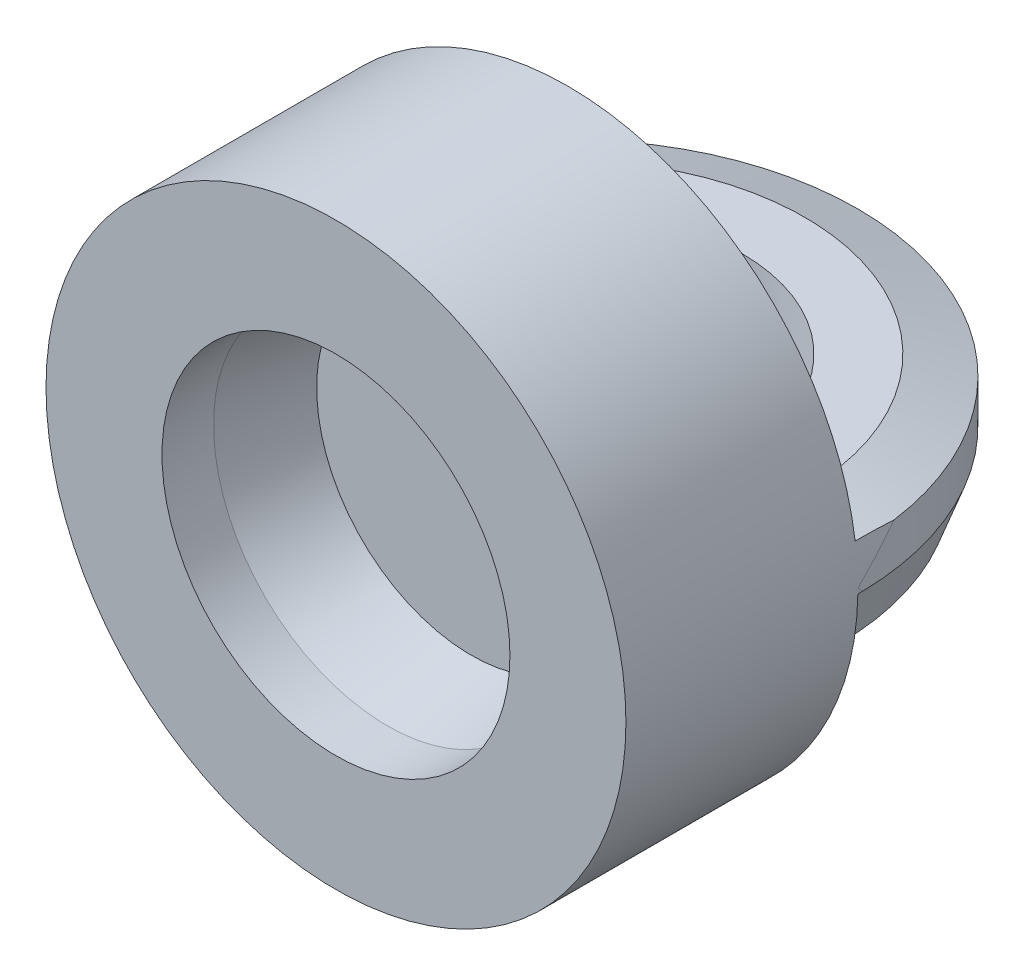
SolidWorks part; units mm, degrees
ref_plane "Front Plane" through (0, 0, 0) normal (0, 0, 1) x (1, 0, 0)
ref_plane "Top Plane" through (0, 0, 0) normal (0, 1, 0) x (1, 0, 0)
ref_plane "Right Plane" through (0, 0, 0) normal (1, 0, 0) x (0, 0, -1)
sketch "Sketch1" plane through (0, 0, 0) normal (0, 0, 1) x (1, 0, 0)
  circle A0 centre (0, 0) radius 7.5
  dimension "D1" = 15
extrude "Boss-Extrude1" add sketch "Sketch1" along normal blind 6
sketch "Sketch2" plane through (0, 0, 6) normal (0, 0, 1) x (1, 0, 0)
  circle A0 centre (0, 0) radius 4.5
  dimension "D1" = 9
extrude "Cut-Extrude1" cut sketch "Sketch2" against normal blind 3.5
chamfer "Chamfer1" distance 0.5 angle 77 1 edges at (4.5, 0, 2.5) first distance on face at (4.5, 0, 2.5)
sketch "Sketch3" plane through (0, 0, 0) normal (0, 1, 0) x (1, 0, 0)
  line L0 (7.5, 0) -> (-7.5, 0) construction
  line L1 (-7.5, 0) -> (-7.5, -6) construction
  line L2 (-7.5, 0) -> (-4.5, 0)
  line L3 (4.5, 0) -> (7.5, 0)
  arc A0 (-4.5, 0) -> (4.5, 0) centre (0, 0) cw
  arc A1 (-7.5, 0) -> (7.5, 0) centre (0, 0) cw
  dimension "D1" = 3
extrude "Boss-Extrude2" add sketch "Sketch3" along normal blind 1.5 and the other way blind 1.5
sketch "Sketch4" plane through (0, 0, 0) normal (0, 0, 1) x (1, 0, 0)
  circle A0 centre (0, 0) radius 7.5 construction
  circle A1 centre (0, 0) radius 7.5
extrude "Cut-Extrude2" cut sketch "Sketch4" against normal through all flip side to cut
chamfer "Chamfer3" distance 0.5 angle 70 2 edges at (0, -1.5, -7.5) (0, 1.5, -7.5) first distance on face at (0, -1.5, -2.25) first distance on face at (0, 0, -3.0025)
